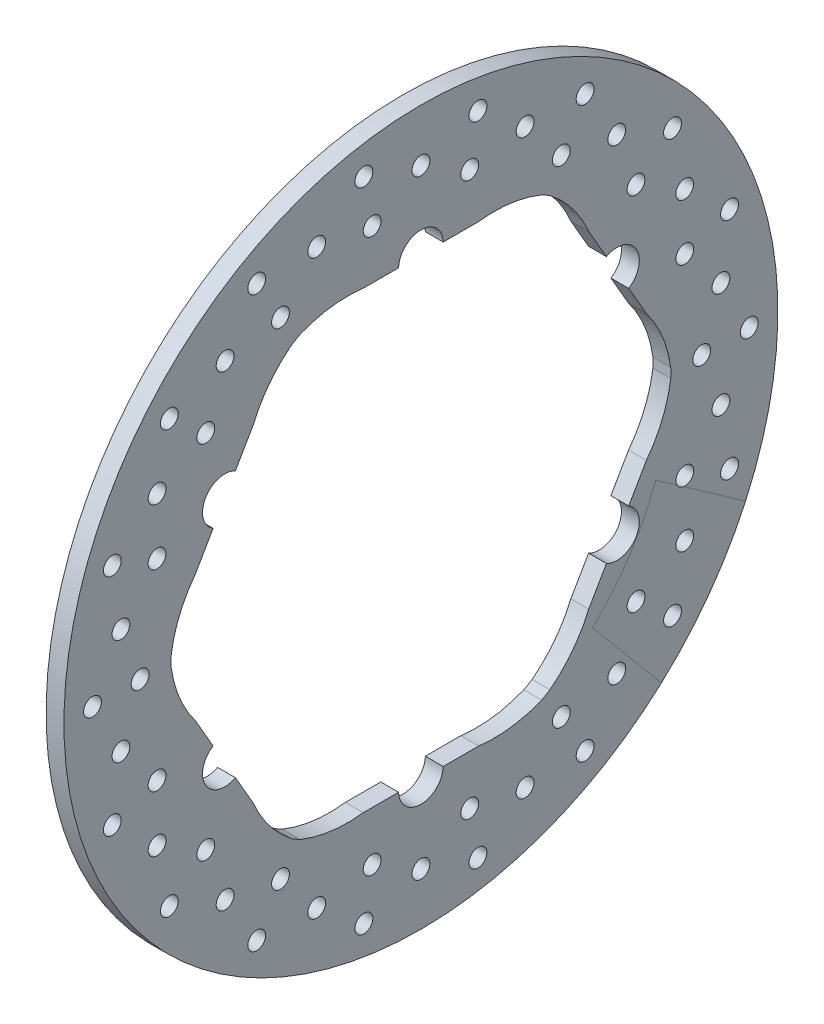
SolidWorks part; units mm, degrees
material "Gray Cast Iron (SN)"
ref_plane "X-Y Datum" through (0, 0, 0) normal (0, 0, 1) x (1, 0, 0)
ref_plane "X-Z Datum" through (0, 0, 0) normal (0, 1, 0) x (1, 0, 0)
ref_plane "Y-Z Datum" through (0, 0, 0) normal (1, 0, 0) x (0, 0, -1)
sketch "Sketch1" plane through (0, 0, 0) normal (1, 0, 0) x (0, 0, -1)
  circle A0 centre (0, 0) radius 95.25
  circle A1 centre (0, 0) radius 66.675
  dimension "D1" = 190.5
  dimension "D2" = 133.35
extrude "Main Rotor" add sketch "Sketch1" along normal blind 4.7625
sketch "Sketch2" plane through (4.7625, 0, 0) normal (1, 0, 0) x (0, 0, -1)
  line L0 (0, 0) -> (-50000, 0) construction
  line L1 (0, 0) -> (-93.8029, 16.54) construction
  line L4 (-82.3453, 29.9712) -> (-70.4112, 25.6276) construction
  circle A2 centre (0, 0) radius 95.25 construction
  circle A72 centre (-80.0452, 14.1141) radius 2.3813
  circle A73 centre (0, 0) radius 66.675 construction
  circle A74 centre (-82.3453, 29.9712) radius 2.3812
  circle A75 centre (-70.4112, 25.6276) radius 2.3813
  circle A76 centre (0, 0) radius 95.25 construction
  circle A77 centre (-70.3905, 40.64) radius 2.3812
  circle A78 centre (-67.1285, 56.3275) radius 2.3813
  circle A79 centre (0, 0) radius 66.675 construction
  circle A80 centre (-57.3997, 48.1641) radius 2.3813
  circle A81 centre (-52.2458, 62.2641) radius 2.3813
  circle A82 centre (-87.63, 0) radius 2.3813
  circle A83 centre (-43.815, 75.8898) radius 2.3812
  circle A84 centre (-37.465, 64.8913) radius 2.3813
  circle A85 centre (-74.93, 0) radius 2.3813
  circle A86 centre (-27.7994, 76.3782) radius 2.3812
  circle A87 centre (-15.2168, 86.2987) radius 2.3813
  circle A88 centre (-13.0115, 73.7916) radius 2.3813
  circle A89 centre (0, 81.28) radius 2.3813
  circle A90 centre (15.2168, 86.2987) radius 2.3813
  circle A91 centre (13.0115, 73.7916) radius 2.3813
  circle A92 centre (27.7994, 76.3782) radius 2.3813
  circle A93 centre (43.815, 75.8898) radius 2.3813
  circle A94 centre (37.465, 64.8913) radius 2.3813
  circle A95 centre (52.2458, 62.2641) radius 2.3813
  circle A96 centre (67.1285, 56.3275) radius 2.3813
  circle A97 centre (57.3997, 48.1641) radius 2.3813
  circle A98 centre (70.3905, 40.64) radius 2.3812
  circle A99 centre (82.3453, 29.9712) radius 2.3813
  circle A100 centre (70.4112, 25.6276) radius 2.3813
  circle A101 centre (80.0452, 14.1141) radius 2.3813
  circle A102 centre (87.63, 0) radius 2.3813
  circle A103 centre (74.93, 0) radius 2.3813
  circle A104 centre (80.0452, -14.1141) radius 2.3813
  circle A105 centre (82.3453, -29.9712) radius 2.3812
  circle A106 centre (70.4112, -25.6276) radius 2.3812
  circle A107 centre (70.3905, -40.64) radius 2.3813
  circle A108 centre (67.1285, -56.3275) radius 2.3812
  circle A109 centre (57.3997, -48.1641) radius 2.3813
  circle A110 centre (52.2458, -62.2641) radius 2.3812
  circle A111 centre (43.815, -75.8898) radius 2.3813
  circle A112 centre (37.465, -64.8913) radius 2.3813
  circle A113 centre (27.7994, -76.3782) radius 2.3813
  circle A114 centre (15.2168, -86.2987) radius 2.3813
  circle A115 centre (13.0115, -73.7916) radius 2.3812
  circle A116 centre (0, -81.28) radius 2.3812
  circle A117 centre (-15.2168, -86.2987) radius 2.3813
  circle A118 centre (-13.0115, -73.7916) radius 2.3813
  circle A119 centre (-27.7994, -76.3782) radius 2.3812
  circle A120 centre (-43.815, -75.8898) radius 2.3813
  circle A121 centre (-37.465, -64.8913) radius 2.3813
  circle A122 centre (-52.2458, -62.2641) radius 2.3813
  circle A123 centre (-67.1285, -56.3275) radius 2.3813
  circle A124 centre (-57.3997, -48.1641) radius 2.3813
  circle A125 centre (-70.3905, -40.64) radius 2.3813
  circle A126 centre (-82.3453, -29.9712) radius 2.3813
  circle A127 centre (-70.4112, -25.6276) radius 2.3813
  circle A128 centre (-80.0452, -14.1141) radius 2.3813
  point P109 (0, 0)
  dimension "D1" = 4.7625
  dimension "D2" = 12.7
  dimension "D3" = 10
  dimension "D5" = 81.28
  dimension "D4" = 87.63
  dimension "D6" = 18
extrude "Cut Slots" cut sketch "Sketch2" against normal through all
sketch "Sketch3" plane through (4.7625, 0, 0) normal (1, 0, 0) x (0, 0, -1)
  line L0 (0.3454, 5.0869) -> (-47951.5604, 14168.94) construction
  line L1 (0, 21.2491) -> (-18.4023, 10.6246)
  line L2 (-18.4023, 10.6246) -> (-18.4023, -10.6246)
  line L3 (-18.4023, -10.6246) -> (0, -21.2491)
  line L4 (0, -21.2491) -> (18.4023, -10.6246)
  line L5 (18.4023, -10.6246) -> (18.4023, 10.6246)
  line L6 (18.4023, 10.6246) -> (0, 21.2491)
  line L7 (0, 0) -> (43301.2702, 25000) construction
  line L8 (0, 0) -> (0, 50000) construction
  line L12 (9.525, -59.2994) -> (-9.525, -59.2994) construction
  line L17 (-30.6007, -53.002) -> (24969.3838, 43248.2414) construction
  line L18 (-60.783, 0) -> (49939.217, 0) construction
  line L19 (0, 0) -> (-25000, 43301.2702) construction
  line L20 (-14.2015, 9.3837) -> (0, 17.583) construction
  line L21 (-1.5875, 20.3326) -> (-2.825, 22.476) construction
  arc A0 (8.6043, -53.0208) -> (15.2264, -60.5686) centre (16.2243, -53.0143) ccw
  circle A1 centre (0, 0) radius 66.675 construction
  arc A7 (-15.2264, -60.5686) -> (-32.2316, -58.3668) centre (-19.5921, -27.5182) cw
  arc A10 (15.2264, -60.5686) -> (32.2316, -58.3668) centre (19.5921, -27.5182) ccw
  arc A19 (-19.6024, -33.9524) -> (-8.6043, -53.0208) centre (-30.6006, -53.0019) cw
  arc A25 (41.6152, -33.9619) -> (44.8408, -43.4707) centre (37.7996, -40.5577) cw
  arc A26 (34.4313, -57.0968) -> (66.6629, -1.27) centre (0, 0) ccw
  arc A27 (50.2195, -19.0589) -> (60.0672, -17.0979) centre (54.0238, -12.4565) ccw
  arc A28 (19.6024, -33.9524) -> (8.6043, -53.0208) centre (30.6006, -53.0019) ccw
  arc A29 (60.0672, 17.0979) -> (50.2195, 19.0589) centre (54.0238, 12.4565) ccw
  arc A30 (-44.8408, -43.4707) -> (-34.4313, -57.0968) centre (-14.0354, -30.7264) ccw
  arc A31 (-19.6024, -33.9524) -> (-41.6152, -33.9619) centre (-30.6006, -53.0019) ccw
  arc A32 (-39.2049, 0) -> (-50.2195, -19.0589) centre (-61.2013, 0) cw
  arc A33 (-60.0672, -17.0979) -> (-66.6629, -1.27) centre (-33.6275, 3.2082) cw
  arc A34 (-60.0672, 17.0979) -> (-66.6629, 1.27) centre (-33.6275, -3.2082) ccw
  arc A35 (44.8408, 43.4707) -> (41.6152, 33.9619) centre (37.7996, 40.5577) cw
  arc A36 (-32.2316, -58.3668) -> (32.2316, -58.3668) centre (0, 0) ccw
  arc A37 (15.2264, 60.5686) -> (8.6043, 53.0208) centre (16.2243, 53.0143) ccw
  arc A38 (-8.6043, 53.0208) -> (-15.2264, 60.5686) centre (-16.2243, 53.0143) ccw
  arc A39 (-44.8408, 43.4707) -> (-41.6152, 33.9619) centre (-37.7996, 40.5577) ccw
  arc A40 (-50.2195, 19.0589) -> (-60.0672, 17.0979) centre (-54.0238, 12.4565) ccw
  arc A41 (-50.2195, -19.0589) -> (-60.0672, -17.0979) centre (-54.0238, -12.4565) cw
  arc A42 (-8.6043, -53.0208) -> (-15.2264, -60.5686) centre (-16.2243, -53.0143) cw
  arc A43 (-41.6152, -33.9619) -> (-44.8408, -43.4707) centre (-37.7996, -40.5577) ccw
  arc A44 (-39.2049, 0) -> (-50.2195, 19.0589) centre (-61.2013, 0) ccw
  arc A45 (-19.6025, 33.9524) -> (-41.6152, 33.9619) centre (-30.6007, 53.0019) cw
  arc A46 (-44.8408, 43.4707) -> (-34.4313, 57.0968) centre (-14.0354, 30.7264) cw
  arc A47 (-15.2264, 60.5686) -> (-32.2316, 58.3668) centre (-19.5921, 27.5182) ccw
  arc A48 (-19.6025, 33.9524) -> (-8.6043, 53.0208) centre (-30.6007, 53.0019) ccw
  arc A49 (19.6024, 33.9524) -> (8.6043, 53.0208) centre (30.6006, 53.0019) cw
  arc A50 (15.2264, 60.5686) -> (32.2316, 58.3668) centre (19.5921, 27.5182) cw
  arc A51 (44.8408, 43.4707) -> (34.4313, 57.0968) centre (14.0354, 30.7264) ccw
  arc A52 (19.6024, 33.9524) -> (41.6152, 33.9619) centre (30.6006, 53.0019) ccw
  arc A53 (39.2049, 0) -> (50.2195, 19.0589) centre (61.2013, 0) cw
  arc A54 (60.0672, 17.0979) -> (66.6629, 1.27) centre (33.6275, -3.2082) cw
  arc A55 (60.0672, -17.0979) -> (66.6629, -1.27) centre (33.6275, 3.2082) ccw
  arc A56 (39.2049, 0) -> (50.2195, -19.0589) centre (61.2013, 0) ccw
  arc A57 (19.6024, -33.9524) -> (41.6152, -33.9619) centre (30.6007, -53.0019) cw
  arc A58 (44.8408, -43.4707) -> (34.4313, -57.0968) centre (14.0354, -30.7264) cw
  circle A59 centre (0, 20.3326) radius 1.5875
  arc A60 (-66.6629, -1.27) -> (-34.4313, -57.0968) centre (0, 0) ccw
  arc A62 (-34.4313, 57.0968) -> (-66.6629, 1.27) centre (0, 0) ccw
  arc A64 (32.2316, 58.3668) -> (-32.2316, 58.3668) centre (0, 0) ccw
  arc A66 (66.6629, 1.27) -> (34.4313, 57.0968) centre (0, 0) ccw
  circle A71 centre (0, 0) radius 7.4362 construction
  circle A72 centre (0, 17.583) radius 3.175 construction
  circle A73 centre (17.6086, 10.1663) radius 1.5875
  circle A74 centre (17.6086, -10.1663) radius 1.5875
  circle A75 centre (0, -20.3326) radius 1.5875
  circle A76 centre (-17.6085, -10.1663) radius 1.5875
  circle A77 centre (-17.6085, 10.1663) radius 1.5875
  point P34 (0, -59.2994)
  point P35 (-9.2012, 15.9369)
  point P116 (0, 0)
  point P124 (0, 0)
  dimension "D2" = 42.799
  dimension "D4" = 7.62
  dimension "D7" = 1.27
  dimension "D8" = 33.3375
  dimension "D9" = 21.9964
  dimension "D10" = 3.175
  dimension "D11" = 3.175
  dimension "D12" = 6.35
  dimension "D13" = 6
  dimension "D1" = 36.8046
  dimension "D3" = 6
  dimension "D6" = 19.05
extrude "Boss-Extrude2" add sketch "Sketch3" against normal up to surface (4.7625 mm away) contours A54 A66 A51 A35 A52 A49 A37 A50 A64 A47 A38 A48 A45 A39 A46 A62 A34 A40 A44 A32 A41 A33 A60 A30 A43 A31 A19 A42 A7 A36 A10 A0 A28 A57 A25 A58 A26 A55 A27 A56 A53 A29 L1 A59 L6 L5 L4 region at (4.7625, -59.2833, -9.0788) up to face at (0, 0, 85.2488)
fillet "Fillet1" [suppressed] radius 3.175
sketch "Sketch4" plane through (0, 0, 0) normal (-1, 0, 0) x (0, 0, 1)
  circle A0 centre (0, 45.212) radius 1.27
  circle A1 centre (39.1547, 22.606) radius 1.27
  circle A2 centre (39.1547, -22.606) radius 1.27
  circle A3 centre (0, -45.212) radius 1.27
  circle A4 centre (-39.1547, -22.606) radius 1.27
  circle A5 centre (-39.1547, 22.606) radius 1.27
  point P16 (0, 0)
  dimension "D1" = 45.212
  dimension "D2" = 2.54
  dimension "D3" = 6
extrude "Cut-Extrude2" cut sketch "Sketch4" against normal through all
sketch "Sketch5" plane through (4.7625, 0, 0) normal (1, 0, 0) x (0, 0, -1)
  line L0 (0, 0) -> (-50000, 0) construction
  line L1 (0, 0) -> (-46984.631, 17101.0072) construction
  line L2 (62.654, -22.8042) -> (86.6311, -39.5931)
  line L3 (45.7933, -48.4616) -> (64.1833, -70.378)
  circle A0 centre (0, 0) radius 95.25 construction
  circle A1 centre (0, 0) radius 66.675 construction
  arc A2 (64.1833, -70.378) -> (86.6311, -39.5931) centre (0, 0) ccw
  arc A3 (45.7933, -48.4616) -> (62.654, -22.8042) centre (0, 0) ccw
  dimension "D1" = 20
  dimension "D2" = 15
  dimension "D3" = 15
  dimension "D4" = 38.1
split line "Split Line1"
ref_axis "Axis1" through (5.0006, 0, 0) along (-1, 0, 0)
sketch "Sketch6" plane through (4.7625, 0, 0) normal (1, 0, 0) x (0, 0, -1)
  line L0 (0, 0) -> (53.7487, 0) construction
  line L1 (0, 43.8283) -> (0, 9.5266) construction
  line L2 (-25.1315, 60.4139) -> (26.8555, 60.4139) construction
  line L3 (-18.4023, 60.5917) -> (-5.9505, 60.5917)
  line L4 (5.9505, 60.5917) -> (18.4023, 60.5917)
  line L5 (-18.4023, 60.5917) -> (-18.4023, 35.1917)
  line L6 (-18.4023, 35.1917) -> (18.4023, 35.1917)
  line L7 (18.4023, 35.1917) -> (18.4023, 60.5917)
  arc A0 (5.9505, 60.5917) -> (-5.9505, 60.5917) centre (0, 60.4139) ccw
  dimension "D2" = 11.9062
  dimension "D1" = 60.4139
  dimension "D3" = 0.3556
  dimension "D4" = 36.8046
  dimension "D5" = 25.4
extrude "FE12 Cut OUt" cut sketch "Sketch6" against normal up to surface (4.7625 mm away) up to face at (0, 0, 0)
pattern_circular "CirPattern1" count 6 over 360 about axis through (4.7625, 0, 0) along (-1, 0, 0) of "FE12 Cut OUt"
sketch "Sketch7" plane through (4.7625, 0, 0) normal (1, 0, 0) x (0, 0, -1)
  circle A0 centre (0, 0) radius 46.99
  dimension "D1" = 93.98
extrude "Cleanup Cut" cut sketch "Sketch7" against normal through all
move or copy body "Body-Move/Copy1" [suppressed] bodies to move or copy 107 parameters "D1"=0, "D2"=0, "D3"=0
